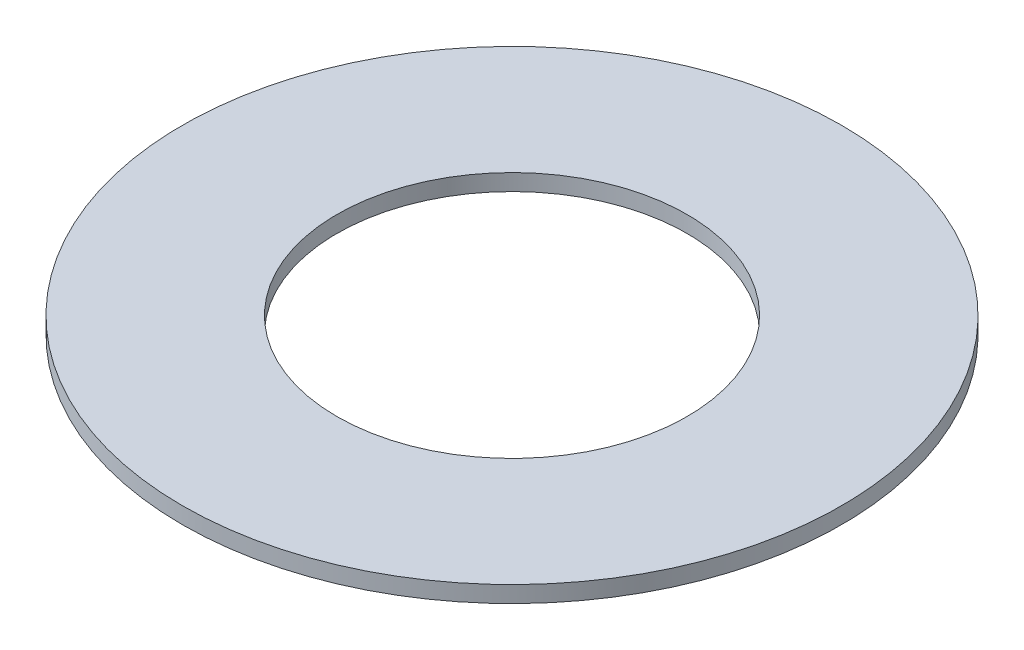
SolidWorks part; units mm, degrees
ref_plane "Front Plane" through (0, 0, 0) normal (0, 0, 1) x (1, 0, 0)
ref_plane "Top Plane" through (0, 0, 0) normal (0, 1, 0) x (1, 0, 0)
ref_plane "Right Plane" through (0, 0, 0) normal (1, 0, 0) x (0, 0, -1)
sketch "Sketch1" plane through (0, 0, 0) normal (0, 1, 0) x (1, 0, 0)
  circle A0 centre (0, 0) radius 80
  dimension "FLANGE_OD" = 160
extrude "Boss-Extrude1" add sketch "Sketch1" along normal blind 4
sketch "Sketch2" plane through (0, 0, 0) normal (0, 1, 0) x (1, 0, 0)
  circle A0 centre (0, 0) radius 42.5
  dimension "BORE_D" = 85
extrude "Cut-Extrude1" cut sketch "Sketch2" along normal through all
sketch "Sketch3" plane through (0, 4, 0) normal (0, 1, 0) x (1, 0, 0)
  circle A0 centre (0, 0) radius 31.9222 construction
  circle A1 centre (-31.9222, 0) radius 5.557
  dimension "BOLT_D" = 11.114
  dimension "BOLT_PCD" = 63.8443
extrude "Cut-Extrude2" cut sketch "Sketch3" against normal blind 3.5708 rebuild error yes
pattern_circular "CirPattern1" count 5 over 360 rebuild error yes
